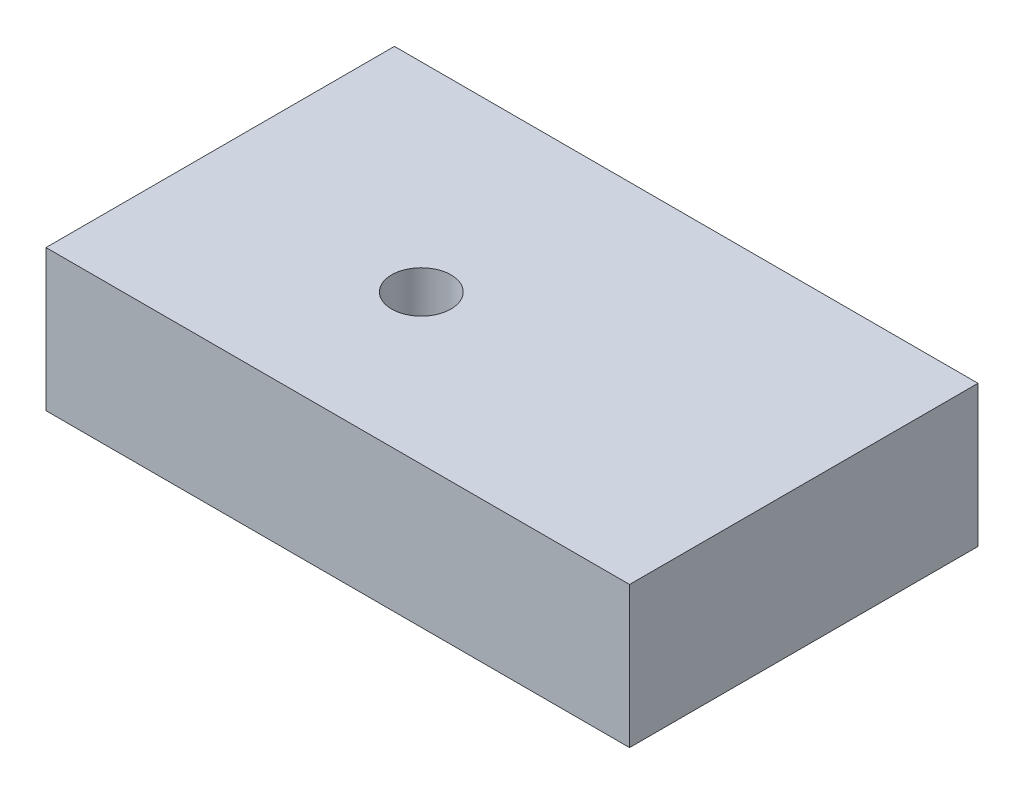
SolidWorks part; units mm, degrees
ref_plane "Front (1)" through (0, 0, 0) normal (0, 0, 1) x (1, 0, 0)
ref_plane "Top (2)" through (0, 0, 0) normal (0, 1, 0) x (1, 0, 0)
ref_plane "Right (3)" through (0, 0, 0) normal (1, 0, 0) x (0, 0, -1)
ref_axis "X Axis" through (13.5064, 0, 0) along (-1, 0, 0)
ref_axis "Y Axis" through (0, 12.3593, 0) along (0, -1, 0)
ref_axis "Z Axis" through (0, 0, 14.1119) along (0, 0, -1)
sketch "Sketch1" plane through (0, 0, 0) normal (0, 1, 0) x (1, 0, 0)
  line L1 (-19.0441, -11.1258) -> (22.2515, -11.1258)
  line L2 (-19.0441, -11.1258) -> (-19.0441, 13.5313)
  line L3 (-19.0441, 13.5313) -> (22.2515, 13.5313)
  line L4 (22.2515, -11.1258) -> (22.2515, 13.5313)
extrude "Boss-Extrude1" add sketch "Sketch1" against normal blind 10
hole_wizard "M5x0.8 Tapped Hole1" positions "Sketch3" profile "Sketch2" tap size "M5x0.8" standard "Ansi Metric"
sketch "Sketch3" plane through (0, 0, 0) normal (0, 1, 0) x (-1, 0, 0)
  point P0 (3.044, 0.5692)
sketch "Sketch2" plane through (-3.044, 0, 0.5692) normal (1, 0, 0) x (0, 0, 1)
  line L0 (0, 0) -> (0, 15.2618)
  line L1 (0, 15.2618) -> (2.1, 14)
  line L2 (2.1, 14) -> (2.1, 0)
  line L5 (2.1, 0) -> (0, 0)
  line L10 (0, 15.2618) -> (-2.1, 14) construction
  line L11 (0, -6.35) -> (0, 107.95) construction
  dimension "Tap Drill Dia." = 4.2
  dimension "Tap Drill Depth" = 14
  dimension "Drill Angle" = 118
cosmetic thread "Hole Thread1" parameters "D1"=10, "D2"=5
